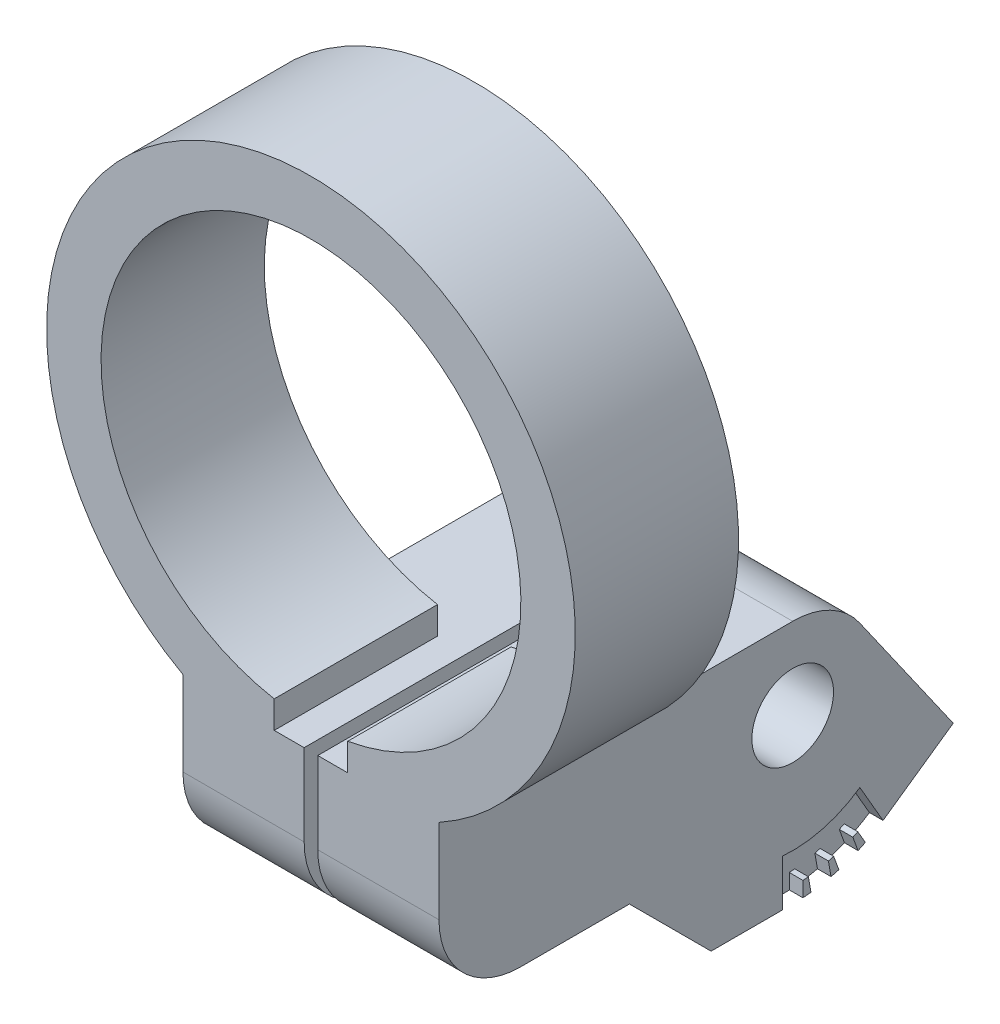
SolidWorks part; units mm, degrees
ref_plane "Front Plane" through (0, 0, 0) normal (0, 0, 1) x (1, 0, 0)
ref_plane "Top Plane" through (0, 0, 0) normal (0, 1, 0) x (1, 0, 0)
ref_plane "Right Plane" through (0, 0, 0) normal (1, 0, 0) x (0, 0, -1)
sketch "Sketch1" plane through (0, 0, 0) normal (0, 0, 1) x (1, 0, 0)
  line L0 (0, 11.4873) -> (0, -15.0157) construction
  line L1 (1.35, -8.5) -> (4.7044, -8.5)
  line L2 (1.35, -8.5) -> (-1.35, -8.5)
  line L3 (1.35, -8.5) -> (1.35, -7.4944)
  line L4 (1.35, -7.4944) -> (-1.35, -7.4944)
  line L5 (-1.35, -8.5) -> (-1.35, -7.4944)
  line L6 (1.35, -8.5) -> (-1.35, -7.4944) construction
  line L7 (1.35, -7.4944) -> (-1.35, -8.5) construction
  line L8 (-1.35, -8.5) -> (-4.7044, -8.5)
  line L9 (-1.35, -8.5) -> (-1.35, -14.6)
  line L10 (-1.35, -14.6) -> (-4.7044, -14.6)
  line L11 (-4.7044, -8.5) -> (-4.7044, -14.6)
  line L12 (1.35, -8.5) -> (1.35, -14.6)
  line L13 (-8.5, -8.5) -> (-1.25, -8.5)
  line L14 (-1.25, -8.5) -> (-1.25, -7.5117)
  line L15 (1.25, -7.5117) -> (1.25, -8.5)
  line L16 (1.25, -8.5) -> (8.5, -8.5)
  line L17 (8.5, -8.5) -> (8.5, -2.45)
  line L18 (8.5, -2.45) -> (10, -2.45)
  line L19 (10, 2.45) -> (8.5, 2.45)
  line L20 (8.5, 2.45) -> (8.5, 8.5)
  line L21 (8.5, 8.5) -> (-8.5, 8.5)
  line L22 (-8.5, 8.5) -> (-8.5, 2.45)
  line L23 (-8.5, 2.45) -> (-10, 2.45)
  line L24 (-10, -2.45) -> (-8.5, -2.45)
  line L25 (-8.5, -2.45) -> (-8.5, -8.5)
  line L26 (-8.5, -8.5) -> (-1.25, -8.5)
  line L27 (-1.25, -8.5) -> (-1.25, -7.5117)
  line L28 (1.25, -7.5117) -> (1.25, -8.5)
  line L29 (1.25, -8.5) -> (8.5, -8.5)
  line L30 (8.5, -8.5) -> (8.5, -2.45)
  line L31 (8.5, -2.45) -> (10, -2.45)
  line L32 (10, 2.45) -> (8.5, 2.45)
  line L33 (8.5, 2.45) -> (8.5, 8.5)
  line L34 (8.5, 8.5) -> (-8.5, 8.5)
  line L35 (-8.5, 8.5) -> (-8.5, 2.45)
  line L36 (-8.5, 2.45) -> (-10, 2.45)
  line L37 (-10, -2.45) -> (-8.5, -2.45)
  line L38 (-8.5, -2.45) -> (-8.5, -8.5)
  line L39 (1.35, -14.6) -> (4.7044, -14.6)
  line L40 (4.7044, -8.5) -> (4.7044, -14.6)
  line L41 (-1.25, -8.0059) -> (-1.35, -8.0059) construction
  line L42 (-1.35, -14.6) -> (-0.25, -14.6)
  line L43 (-1.35, -14.6) -> (-1.35, -8.6)
  line L44 (-1.35, -8.6) -> (-0.25, -8.6)
  line L45 (-0.25, -14.6) -> (-0.25, -8.6)
  line L46 (7.715, 0) -> (7.615, 0) construction
  line L47 (-1.25, -8.5) -> (-1.25, -8.6) construction
  line L48 (-1.35, -8.5) -> (1.35, -8.5)
  line L49 (-1.35, -8.5) -> (-1.35, -8.6)
  line L50 (-1.35, -8.6) -> (1.35, -8.6)
  line L51 (1.35, -8.5) -> (1.35, -8.6)
  line L52 (1.35, -8.6) -> (0.25, -8.6)
  line L53 (0.25, -14.6) -> (0.25, -8.6)
  line L54 (1.35, -14.6) -> (0.25, -14.6)
  circle A0 centre (0, 0) radius 7.715
  circle A1 centre (0, 0) radius 9.715
  arc A3 (1.25, -7.5117) -> (-1.25, -7.5117) centre (0, 0) ccw
  arc A4 (10, -2.45) -> (10, 2.45) centre (10, 0) ccw
  arc A5 (-10, 2.45) -> (-10, -2.45) centre (-10, 0) ccw
  arc A6 (1.25, -7.5117) -> (-1.25, -7.5117) centre (0, 0) ccw
  arc A7 (10, -2.45) -> (10, 2.45) centre (10, 0) ccw
  arc A8 (-10, 2.45) -> (-10, -2.45) centre (-10, 0) ccw
  point P10 (0, -7.9972)
  dimension "D2" = 0.1
  dimension "D4" = 2
  dimension "D3" = 0.5
  dimension "D5" = 6
  dimension "D1" = 0
extrude "Shape" add sketch "Sketch1" along normal blind 6 contours L36 A8 L37 L38 L26 L27 A0 L28 L29 L30 L31 A7 L32 L33 L34 L35 | A7 A1 L33 L32 | A7 L31 L30 A1 | A8 A1 L38 L37 | A8 L36 L35 A1 | L34 A1 | L8 A1 L9 | L12 A1 L1 | A1 L12 L39 L40 | A1 L11 L10 L9 | L9 A1 L45 L44 | A1 L43 L42 L45 | A1 L53 L54 L12 | L53 A1 L12 L50
sketch "Sketch3" plane through (0, 0, 0) normal (0, 0, -1) x (-1, 0, 0)
  line L1 (-4.7044, -14.6) -> (-0.25, -14.6)
  line L2 (-4.7044, -14.6) -> (-4.7044, -8.6)
  line L3 (-4.7044, -8.6) -> (-0.25, -8.6)
  line L4 (-0.25, -14.6) -> (-0.25, -8.6)
  line L5 (4.7044, -14.6) -> (0.25, -14.6)
  line L6 (4.7044, -14.6) -> (4.7044, -8.6)
  line L7 (4.7044, -8.6) -> (0.25, -8.6)
  line L8 (0.25, -14.6) -> (0.25, -8.6)
extrude "Lever" add sketch "Sketch3" along normal blind 10
sketch "Sketch2" plane through (4.7044, 0, 0) normal (1, 0, 0) x (0, 0, -1)
  line L0 (-6, -11.6) -> (10, -11.6) construction
  line L4 (10, -8.6) -> (0, -8.6) construction
  line L5 (10, -8.6) -> (-6, -8.6)
  line L6 (10, -8.6) -> (10, -14.6)
  line L7 (10, -14.6) -> (-6, -14.6)
  line L8 (-6, -8.6) -> (-6, -14.6)
  circle A0 centre (7, -11.6) radius 3
  circle A1 centre (7, -11.6) radius 1.5
  circle A2 centre (-3, -11.6) radius 3
  dimension "D1" = 3
extrude "Cuts" cut sketch "Sketch2" against normal up to surface (9.4088 mm away)
sketch "Sketch5" plane through (-4.7044, 0, 0) normal (-1, 0, 0) x (0, 0, 1)
  line L0 (-7, -17.6) -> (-4, -17.6)
  line L1 (-4, -17.6) -> (-4, -14.6)
  line L2 (3, -14.6) -> (-7, -14.6) construction
  line L3 (-7, -11.6) -> (-10.4415, -16.5149)
  line L4 (-7, -11.6) -> (-7, -14.6) construction
  line L5 (-10.4415, -16.5149) -> (-12.8989, -14.7942)
  line L6 (-12.8989, -14.7942) -> (-9.4575, -9.8793)
  line L7 (-7, -17.6) -> (-7, -14.6)
  line L8 (-4, -17.6) -> (-1, -14.6)
  circle A0 centre (-7, -11.6) radius 6
  arc A1 (-7, -8.6) -> (-7, -14.6) centre (-7, -11.6) ccw construction
  arc M8 (-7, -8.6) -> (-7, -14.6) centre (-7, -11.6) ccw
  line M9 (-7, -14.6) -> (3, -14.6)
  dimension "D1" = 12
  dimension "D2" = 45
  dimension "D3" = 35
extrude "Limits 1" add sketch "Sketch5" against normal up to surface (4.4544 mm away) contours A0 L0 L1 | L7 A0 L1 M9 | L6 A0 L3 M8 | A0 L6 L5 | L3 A0 L7 M8 | A0 L1 L8 M9 | L1 A0 M9 up to face at (-0.25, -11.6, -5.5)
sketch "Sketch6" plane through (4.7044, 0, 0) normal (1, 0, 0) x (0, 0, -1)
  line L0 (-3, -14.6) -> (7, -14.6) construction
  line L1 (-3, -14.6) -> (7, -14.6)
  line L7 (-3, -14.6) -> (1, -14.6)
  line L8 (1, -14.6) -> (4, -17.6)
  line L9 (4, -17.6) -> (7, -17.6)
  line L10 (10.4415, -16.5149) -> (12.8989, -14.7942)
  line L11 (12.8989, -14.7942) -> (9.4575, -9.8793)
  line L12 (7, -8.6) -> (-6, -8.6)
  line L13 (-6, -8.6) -> (-6, -11.6)
  line L14 (-3, -14.6) -> (1, -14.6)
  line L15 (1, -14.6) -> (4, -17.6)
  line L16 (4, -17.6) -> (7, -17.6)
  line L17 (10.4415, -16.5149) -> (12.8989, -14.7942)
  line L18 (12.8989, -14.7942) -> (9.4575, -9.8793)
  line L19 (7, -8.6) -> (-6, -8.6)
  line L20 (-6, -8.6) -> (-6, -11.6)
  arc A0 (7, -14.6) -> (7, -8.6) centre (7, -11.6) ccw construction
  arc A1 (7, -14.6) -> (7, -8.6) centre (7, -11.6) ccw
  arc A3 (7, -17.6) -> (10.4415, -16.5149) centre (7, -11.6) ccw
  arc A4 (9.4575, -9.8793) -> (7, -8.6) centre (7, -11.6) ccw
  arc A5 (-6, -11.6) -> (-3, -14.6) centre (-3, -11.6) ccw
  arc A6 (7, -17.6) -> (10.4415, -16.5149) centre (7, -11.6) ccw
  arc A7 (9.4575, -9.8793) -> (7, -8.6) centre (7, -11.6) ccw
  arc A8 (-6, -11.6) -> (-3, -14.6) centre (-3, -11.6) ccw
  dimension "D1" = 0
extrude "Limits 2" add sketch "Sketch6" against normal up to surface (4.4544 mm away) up to face at (0.25, -13.1, -7)
sketch "Sketch7" plane through (-4.7044, 0, 0) normal (-1, 0, 0) x (0, 0, 1)
  line L0 (-7, -11.6) -> (-7, -17.6) construction
  line L1 (-7, -17.6) -> (-4, -17.6) construction
  line L2 (-8.4112, -17.4437) -> (-7.6726, -17.574)
  line L3 (-7.375, -15.8863) -> (-7.6726, -17.574)
  line L4 (-7.375, -15.8863) -> (-6.625, -15.8863)
  line L5 (-7.375, -15.8863) -> (-7.375, -17.6)
  line L6 (-7.375, -17.6) -> (-6.625, -17.6)
  line L7 (-6.625, -15.8863) -> (-6.625, -17.6)
  line L8 (-7.375, -15.8863) -> (-6.625, -17.6) construction
  line L9 (-7.375, -17.6) -> (-6.625, -15.8863) construction
  line L10 (-8.1136, -15.756) -> (-7.375, -15.8863)
  line L11 (-8.1136, -15.756) -> (-8.4112, -17.4437)
  line L12 (-9.4045, -17.1099) -> (-8.6997, -17.3664)
  line L13 (-8.1136, -15.756) -> (-8.6997, -17.3664)
  line L14 (-8.8184, -15.4995) -> (-8.1136, -15.756)
  line L15 (-8.8184, -15.4995) -> (-9.4045, -17.1099)
  line L16 (-10.3248, -16.6087) -> (-9.6752, -16.9837)
  line L17 (-8.8184, -15.4995) -> (-9.6752, -16.9837)
  line L18 (-9.4679, -15.1245) -> (-8.8184, -15.4995)
  line L19 (-9.4679, -15.1245) -> (-10.3248, -16.6087)
  line L20 (-7, -11.6) -> (-6.625, -15.8863) construction
  line L21 (-7, -11.6) -> (-7.375, -15.8863) construction
  line L22 (-8.1136, -15.756) -> (-9.4679, -15.1245) construction
  line L23 (-9.2108, -16.5777) -> (-9.3921, -16.4932) construction
  arc A0 (-10.4415, -16.5149) -> (-7, -17.6) centre (-7, -11.6) ccw construction
  circle A1 centre (-7, -11.6) radius 5.4466
  circle A2 centre (-7, -11.6) radius 4.3026
  point P5 (-7, -16.7431)
  arc M29 (-10.4415, -16.5149) -> (-7, -17.6) centre (-7, -11.6) ccw
  line M30 (-7, -17.6) -> (-4, -17.6)
  dimension "D1" = 0.2
  dimension "D2" = 0.75
  dimension "D4" = 10
  dimension "D3" = 4
extrude "Angle fix 1" cut sketch "Sketch7" against normal blind 0.5 contours L7 L4 L5 M29 M30 | L10 L11 L3 M29 | L14 L15 L13 M29 | L18 L19 L17 M29 | L19 A1 L17 L18 | L17 A1 L15 | L15 A1 L13 L14 | L13 A1 L11 | L11 A1 L3 L10 | L3 A1 L5 | L5 A1 L7 L4
mirror "Angle fix 2" about plane through (0, 0, 0) normal (1, 0, 0) of "Angle fix 1"
